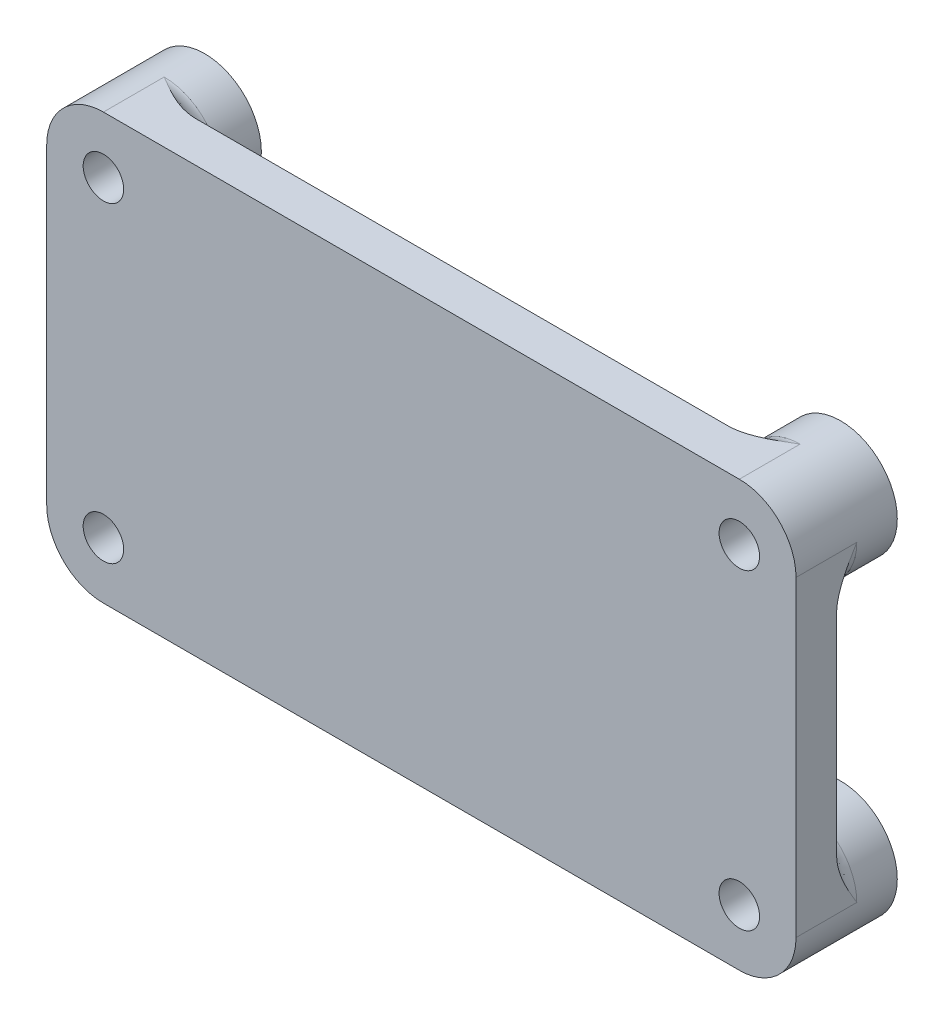
SolidWorks part; units mm, degrees
ref_plane "Спереди" through (0, 0, 0) normal (0, 0, 1) x (1, 0, 0)
ref_plane "Сверху" through (0, 0, 0) normal (0, 1, 0) x (1, 0, 0)
ref_plane "Справа" through (0, 0, 0) normal (1, 0, 0) x (0, 0, -1)
sketch "Эскиз1" plane through (0, 0, 0) normal (0, 0, 1) x (1, 0, 0)
  line L0 (-15.7, 10.5) -> (15.7, 10.5)
  line L5 (-15.7, 7.7) -> (15.7, 7.7) construction
  line L6 (-15.7, 7.7) -> (-15.7, -7.7) construction
  line L7 (-15.7, -7.7) -> (15.7, -7.7) construction
  line L8 (15.7, 7.7) -> (15.7, -7.7) construction
  line L9 (-15.7, 7.7) -> (15.7, -7.7) construction
  line L10 (-15.7, -7.7) -> (15.7, 7.7) construction
  line L14 (-15.7, -10.5) -> (15.7, -10.5)
  line L16 (-18.5, 7.7) -> (-18.5, -7.7)
  line L17 (18.5, 7.7) -> (18.5, -7.7)
  circle A0 centre (15.7, 7.7) radius 2.8
  circle A1 centre (15.7, -7.7) radius 2.8
  circle A2 centre (-15.7, -7.7) radius 2.8
  circle A3 centre (-15.7, 7.7) radius 2.8
  circle A8 centre (15.7, 7.7) radius 1
  circle A9 centre (-15.7, -7.7) radius 1
  circle A10 centre (-15.7, 7.7) radius 1
  circle A11 centre (15.7, -7.7) radius 1
  point P4 (0, 0)
  point P18 (0, 0)
  point P20 (12.9077, -4.9)
  dimension "D3" = 5.6
  dimension "D4" = 2
  dimension "D1" = 31.4
  dimension "D2" = 15.4
extrude "Основа" add sketch "Эскиз1" against normal blind 2 contours A3 A2 L14 A1 A0 L0 region at (0, 0, 0)
extrude "Стойки" add sketch "Эскиз1<5>" against normal blind 5 contours A3 | A0 | A1 | A2 region at (-13.7761, 9.6239, 0) region at (17.6239, 9.6239, 0) region at (-15.7, -4.9792, 0) region at (17.6239, -9.6239, 0)
sketch "Эскиз1<5>" plane through (0, 0, 0) normal (0, 0, 1) x (1, 0, 0) same geometry as "Эскиз1"
fillet "Скругление1" radius 1 4 edges at (-13.7201, -5.7201, -2) (13.7201, -5.7201, -2) (-13.7201, 5.7201, -2) (13.7201, 5.7201, -2)
